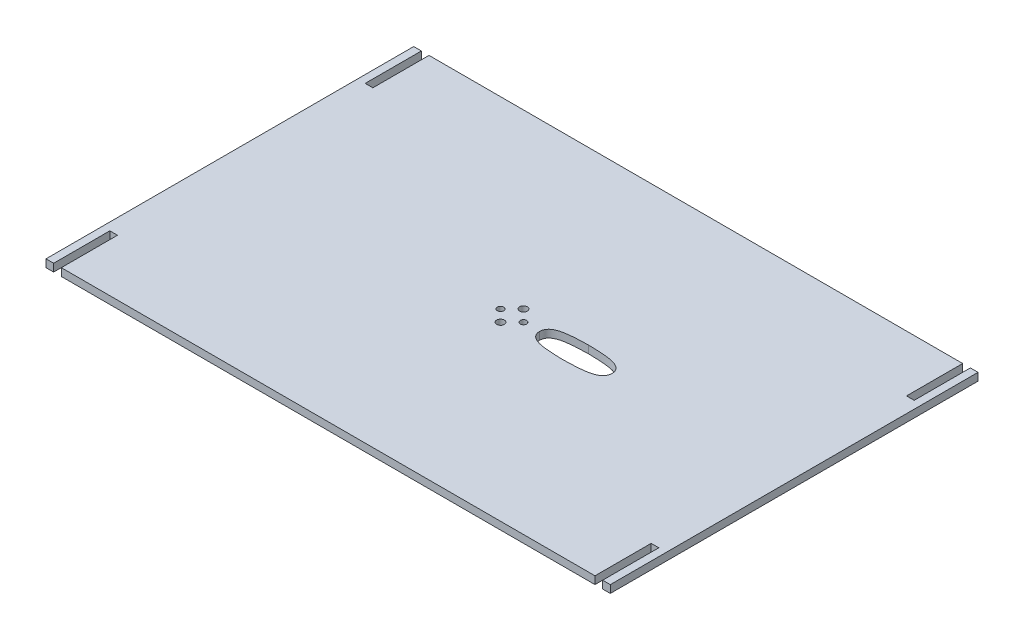
SolidWorks part; units mm, degrees
ref_plane "Front" through (0, 0, 0) normal (0, 0, 1) x (1, 0, 0)
ref_plane "Top" through (0, 0, 0) normal (0, 1, 0) x (1, 0, 0)
ref_plane "Right" through (0, 0, 0) normal (1, 0, 0) x (0, 0, -1)
sketch "Sketch1" plane through (0, 0, 0) normal (0, 1, 0) x (1, 0, 0)
  line L0 (418, 244) -> (424, 244)
  line L1 (0, 0) -> (418, 0)
  line L3 (0, 288) -> (418, 288)
  line L6 (424, 44) -> (418, 44)
  line L7 (418, 0) -> (418, 44)
  line L8 (418, 244) -> (418, 288)
  line L9 (0, 288) -> (0, 244)
  line L10 (-6, 244) -> (-6, 288)
  line L11 (0, 244) -> (-6, 244)
  line L12 (-6, 288) -> (-12, 288)
  line L14 (-6, 44) -> (0, 44)
  line L15 (0, 44) -> (0, 0)
  line L17 (-12, 288) -> (-12, 0)
  line L19 (-6, 44) -> (-6, 0)
  line L20 (-6, 0) -> (-12, 0)
  line L21 (424, 244) -> (424, 288)
  line L22 (424, 288) -> (430, 288)
  line L23 (430, 288) -> (430, 0)
  line L24 (430, 0) -> (424, 0)
  line L26 (424, 0) -> (424, 44)
  dimension "D1" = 6
  dimension "D2" = 6
  dimension "D3" = 6
  dimension "D4" = 288
  dimension "D5" = 418
  dimension "D6" = 200
  dimension "D7" = 12
  dimension "D8" = 430
  dimension "D9" = 12
  dimension "D10" = 44
  dimension "D11" = 6
extrude "Boss-Extrude1" add sketch "Sketch1" along normal blind 6
sketch "Sketch2" plane through (0, 6, 0) normal (0, 1, 0) x (1, 0, 0)
  line L0 (418, 288) -> (0, 288) construction
  line L1 (209, 153) -> (209, 135) construction
  line L2 (200, 144) -> (218, 144) construction
  line L3 (430, 0) -> (430, 288) construction
  line L4 (230.5, 144) -> (259, 144) construction
  line L5 (230.5, 154) -> (287.5, 154) construction
  line L6 (230.5, 154) -> (230.5, 134) construction
  line L7 (230.5, 134) -> (287.5, 134) construction
  line L8 (287.5, 154) -> (287.5, 134) construction
  line L9 (230.5, 154) -> (287.5, 134) construction
  line L10 (230.5, 134) -> (287.5, 154) construction
  line L11 (259, 144) -> (259, 154) construction
  circle A1 centre (209, 135) radius 3
  circle A2 centre (209, 153) radius 3
  circle A3 centre (200, 144) radius 2.5
  circle A4 centre (218, 144) radius 2.5
  spline S0 degree 3 poles (259, 154) (240.9785, 153.6663) (230.9333, 152.4469) (230.5, 144) knots 0 0 0 0 1 1 1 1
  spline S1 degree 3 poles (259, 154) (277.0215, 153.6663) (287.0667, 152.4469) (287.5, 144) knots 0 0 0 0 1 1 1 1
  spline S2 degree 3 poles (259, 134) (277.0215, 134.3337) (287.0667, 135.5531) (287.5, 144) knots 0 0 0 0 1 1 1 1
  spline S3 degree 3 poles (259, 134) (240.9785, 134.3337) (230.9333, 135.5531) (230.5, 144) knots 0 0 0 0 1 1 1 1
  point P0 (209, 144)
  point P9 (259, 144)
  point P23 (0, 0)
  dimension "D1" = 9
  dimension "D4" = 6
  dimension "D5" = 5
  dimension "D7" = 18
  dimension "D8" = 144
  dimension "D9" = 57
  dimension "D10" = 20
  dimension "D3" = 9
  dimension "D11" = 50
  dimension "D2" = 221
  dimension "D6" = 18
extrude "Cut-Extrude1" cut sketch "Sketch2" against normal blind 6
